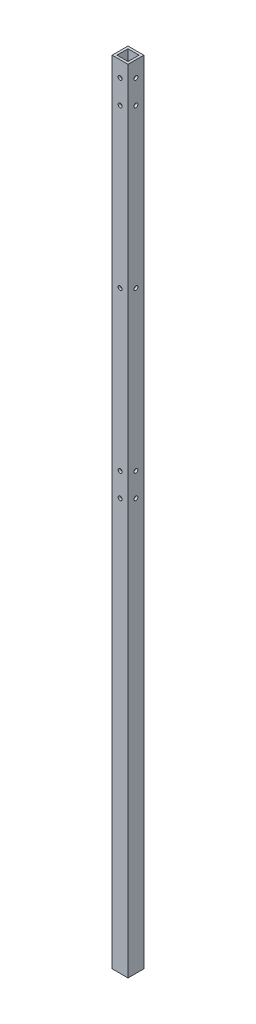
SolidWorks part; units mm, degrees
material "1060 Alloy"
ref_plane "Front Plane" through (0, 0, 0) normal (0, 0, 1) x (1, 0, 0)
ref_plane "Top Plane" through (0, 0, 0) normal (0, 1, 0) x (1, 0, 0)
ref_plane "Right Plane" through (0, 0, 0) normal (1, 0, 0) x (0, 0, -1)
sketch "Sketch1" plane through (0, 0, 0) normal (0, 1, 0) x (1, 0, 0)
  line L1 (0, 0) -> (20, 0)
  line L2 (0, 0) -> (0, 20)
  line L3 (0, 20) -> (20, 20)
  line L4 (20, 0) -> (20, 20)
  line L5 (3, 17) -> (17, 17)
  line L6 (3, 17) -> (3, 3)
  line L7 (3, 3) -> (17, 3)
  line L8 (17, 17) -> (17, 3)
  dimension "D1" = 20
  dimension "D2" = 20
  dimension "D3" = 14
  dimension "D4" = 14
  dimension "D5" = 3
  dimension "D6" = 3
extrude "Boss-Extrude1" add sketch "Sketch1" along normal blind 1000
sketch "Sketch3" plane through (20, 0, 0) normal (1, 0, 0) x (0, 0, -1)
  line L0 (0, 1000) -> (20, 1000) construction
  line L2 (0, 1000) -> (0, 0) construction
  circle A0 centre (10, 980) radius 2.5
  dimension "D3" = 5
  dimension "D1" = 20
  dimension "D2" = 10
extrude "Cut-Extrude1" cut sketch "Sketch3" against normal blind 10 contours A0
pattern_linear "LPattern1" count 3 spacing 230 along (0, -1, 0) of "Cut-Extrude1"
sketch "Sketch4" plane through (0, 1000, 0) normal (0, 1, 0) x (1, 0, 0)
  line L1 (0, 0) -> (10, 10)
  point P1 (0, 0)
sketch "Sketch5" plane through (0, 0, 0) normal (0, -1, 0) x (1, 0, 0)
  line L0 (0, -20) -> (10, -10)
ref_axis "Axis1" through (10, 1000, -10) along (0, -1, 0)
pattern_circular "CirPattern1" count 3 every 90 about axis through (10, 1000, -10) along (0, -1, 0) of "LPattern1"
sketch "Sketch6" plane through (20, 0, 0) normal (1, 0, 0) x (0, 0, -1)
  line L0 (10, 1000) -> (10, 0) construction
  line L1 (0, 1000) -> (10, 1000) construction
  circle A0 centre (10, 950) radius 2.5
  point P4 (0, 0)
  point P5 (0, 0)
  point P6 (0, 0)
  dimension "D3" = 5
  dimension "D1" = 0
  dimension "D2" = 50
extrude "Cut-Extrude2" cut sketch "Sketch6" against normal blind 10 contours A0
pattern_linear "LPattern2" count 2 spacing 400 along (0, -1, 0) of "Cut-Extrude2"
pattern_circular "CirPattern2" count 3 every 90 about axis through (10, 1000, -10) along (0, -1, 0) of "LPattern2"
